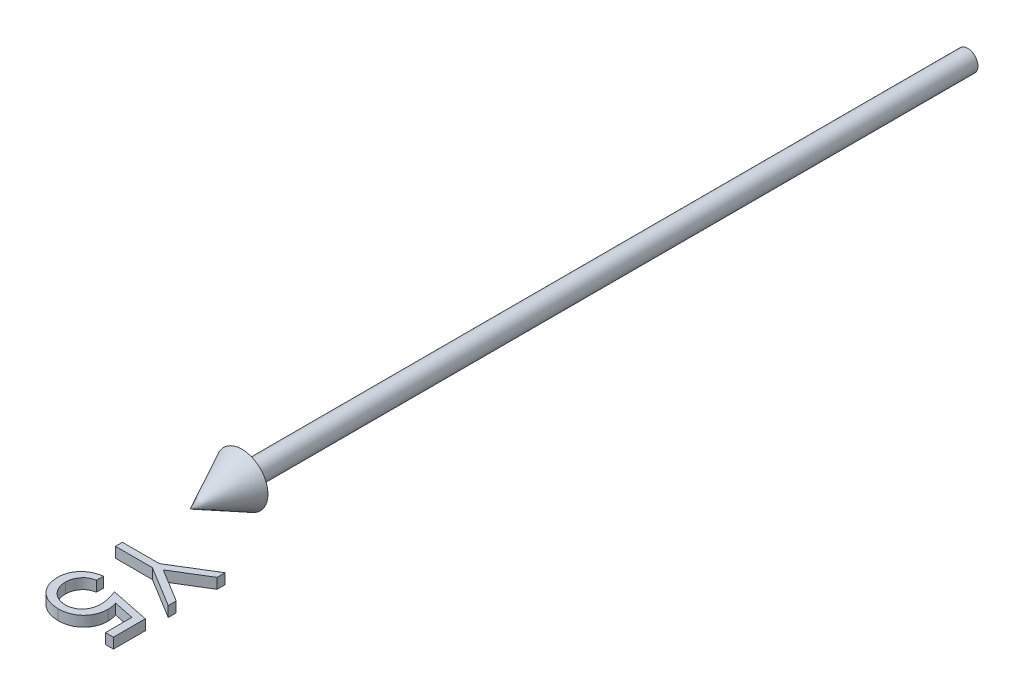
SolidWorks part; units mm, degrees
ref_plane "Front Plane" through (0, 0, 0) normal (0, 0, 1) x (1, 0, 0)
ref_plane "Top Plane" through (0, 0, 0) normal (0, 1, 0) x (1, 0, 0)
ref_plane "Right Plane" through (0, 0, 0) normal (1, 0, 0) x (0, 0, -1)
sketch "Sketch2" plane through (0, 0, 0) normal (0, 1, 0) x (1, 0, 0)
  line L0 (0, 41.95) -> (0, -114.4521) construction
  line L1 (-36.8894, 0) -> (41.4965, 0) construction
  line L2 (0, -150) -> (5, -140)
  line L3 (5, -140) -> (2, -140)
  line L4 (2, -140) -> (2, 0)
  line L5 (2, 0) -> (0, 0)
  line L6 (0, 0) -> (0, -150)
  dimension "D1" = 150
  dimension "D2" = 2
  dimension "D3" = 10
  dimension "D4" = 5
revolve "Revolve1" add sketch "Sketch2" angle 360 about L0
sketch "Sketch3" plane through (0, 0, 0) normal (0, 1, 0) x (1, 0, 0)
  line L0 (0, -157.5) -> (0, -226.675) construction
  line L1 (-19.1041, 0) -> (34.5418, 0) construction
  text T0 "Y5\r\n\r\n\r\n" font "Century Gothic" height 15
  dimension "D1" = 157.5
extrude "Boss-Extrude1" add sketch "Sketch3" against normal blind 1 and the other way blind 1 separate body
equation "\"D1@Sketch2\"=\"frame_arrow_length\""
equation "\"D2@Sketch2\"=\"frame_arrow_odA\"/2"
equation "\"D4@Sketch2\"=\"frame_arrow_head_od\""
equation "\"D3@Sketch2\"=\"frame_arrow_head_length\""
equation "\"frame_arrow_length\"=150"
equation "\"frame_arrow_head_length\"=10"
equation "\"frame_arrow_head_od\"=5"
equation "\"frame_arrow_odA\"=4"
equation "\"D1@Sketch3\"=\"frame_arrow_length\"*1.05"
